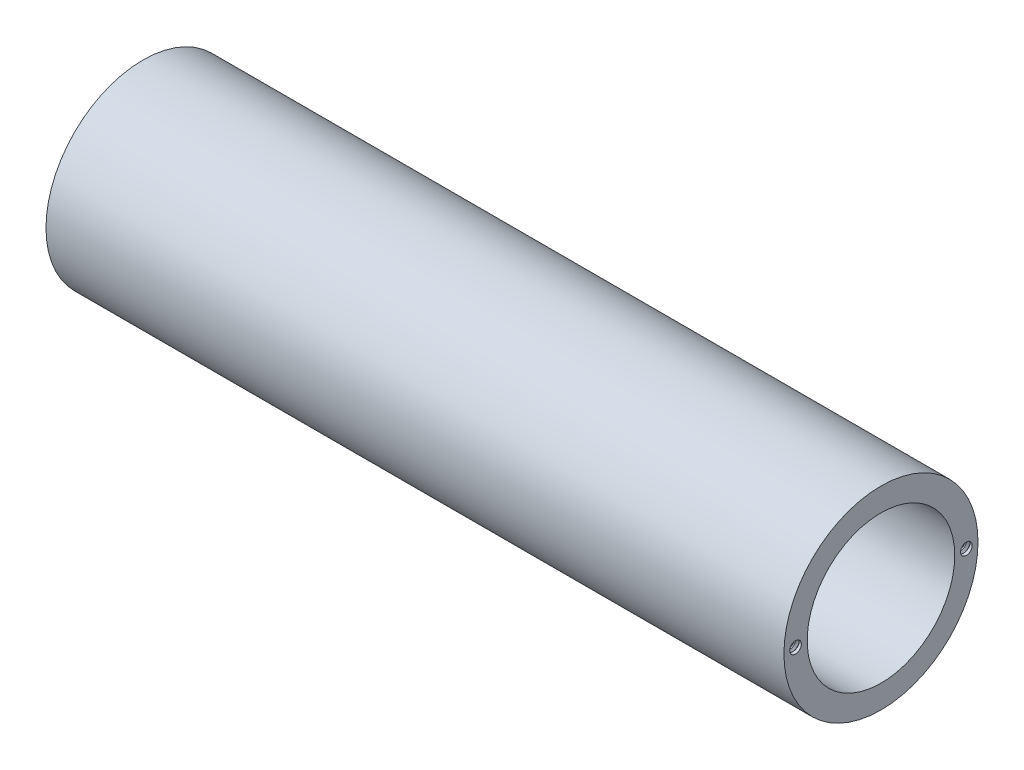
SolidWorks part; units mm, degrees
material "6061-T6 (SS)"
ref_plane "Front Plane" through (0, 0, 0) normal (0, 0, 1) x (1, 0, 0)
ref_plane "Top Plane" through (0, 0, 0) normal (0, 1, 0) x (1, 0, 0)
ref_plane "Right Plane" through (0, 0, 0) normal (1, 0, 0) x (0, 0, -1)
sketch "Sketch1" plane through (0, 0, 0) normal (1, 0, 0) x (0, 0, -1)
  circle A0 centre (0, 0) radius 16.7005
  circle A1 centre (0, 0) radius 12.7
  dimension "D1" = 33.401
  dimension "D2" = 25.4
extrude "Boss-Extrude1" add sketch "Sketch1" along normal blind 127
ref_plane "Plane1" through (70.8, 0, 0) normal (1, 0, 0) x (0, 0, -1)
sketch "Sketch3" plane through (70.8, 0, 0) normal (1, 0, 0) x (0, 0, -1)
  line L0 (-2.54, 5.8199) -> (-2.54, 13.9662)
  line L3 (-2.54, 13.9662) -> (2.54, 13.9662)
  line L4 (2.54, 5.8199) -> (2.54, 13.9662)
  line L5 (3.7702, -5.1096) -> (10.8251, -9.1828)
  line L6 (13.3651, -4.7834) -> (10.8251, -9.1828)
  line L7 (6.3102, -0.7102) -> (13.3651, -4.7834)
  line L8 (-6.3102, -0.7102) -> (-13.3651, -4.7834)
  line L9 (-10.8251, -9.1828) -> (-13.3651, -4.7834)
  line L10 (-3.7702, -5.1096) -> (-10.8251, -9.1828)
  arc A0 (-2.54, 5.8199) -> (-6.3102, -0.7102) centre (0, 0) ccw
  arc A1 (6.3102, -0.7102) -> (2.54, 5.8199) centre (0, 0) ccw
  arc A2 (-3.7702, -5.1096) -> (3.7702, -5.1096) centre (0, 0) ccw
  point P18 (0, 0)
  dimension "D1" = 12.7
  dimension "D2" = 5.08
  dimension "D3" = 3
extrude "Boss-Extrude2" add sketch "Sketch3" against normal blind 5.08
sketch "Sketch4" plane through (127, 0, 0) normal (1, 0, 0) x (0, 0, -1)
  line L0 (-24.0302, 0) -> (24.0302, 0) construction
  line L1 (0, -17.8379) -> (0, 17.8379) construction
  circle A0 centre (14.7003, 0) radius 1
  circle A1 centre (-14.7003, 0) radius 1
  point P6 (0, 0)
  point P12 (0, 0)
  dimension "D2" = 2
  dimension "D1" = 14.7003
extrude "Cut-Extrude1" cut sketch "Sketch4" against normal blind 2.54
thread "Thread1" pitch 0.7937 method cut profile "Thread Profile1" start angle 0, offset 0, length 0, pitch 0.7937, diameter 2
ref_plane "Plane2" through (127, 0, -13.7003) normal (0, -1, 0) x (0, 0, 1)
sketch "Thread Profile1" plane through (127, 0, -13.7003) normal (0, -1, 0) x (0, 0, 1)
  line L0 (0, 0) -> (0, 0.7937) construction
  line L1 (0, 0) -> (0.4296, 0.248)
  line L2 (0.4296, 0.248) -> (0.4296, 0.3473)
  line L3 (0.4296, 0.3473) -> (0, 0.5953)
  line L4 (0.4296, 0.2977) -> (0, 0.2977) construction
  line L11 (0, 0) -> (0, 0.5953)
  point P2 (0, 0)
  dimension "Pitch" = 0.7937
  dimension "Profile_Angle" = 60
  dimension "Profile_Land" = 0.0992
  dimension "Profile_Height" = 0.4296
thread "Thread2" pitch 0.7937 method cut profile "Thread Profile2" start angle 0, offset 0, length 0, pitch 0.7937, diameter 2
ref_plane "Plane3" through (127, 0, 15.7002) normal (0, -1, 0) x (0, 0, 1)
sketch "Thread Profile2" plane through (127, 0, 15.7002) normal (0, -1, 0) x (0, 0, 1)
  line L0 (0, 0) -> (0, 0.7937) construction
  line L1 (0, 0) -> (0.4296, 0.248)
  line L2 (0.4296, 0.248) -> (0.4296, 0.3473)
  line L3 (0.4296, 0.3473) -> (0, 0.5953)
  line L4 (0.4296, 0.2977) -> (0, 0.2977) construction
  line L11 (0, 0) -> (0, 0.5953)
  point P2 (0, 0)
  dimension "Pitch" = 0.7937
  dimension "Profile_Angle" = 60
  dimension "Profile_Land" = 0.0992
  dimension "Profile_Height" = 0.4296
